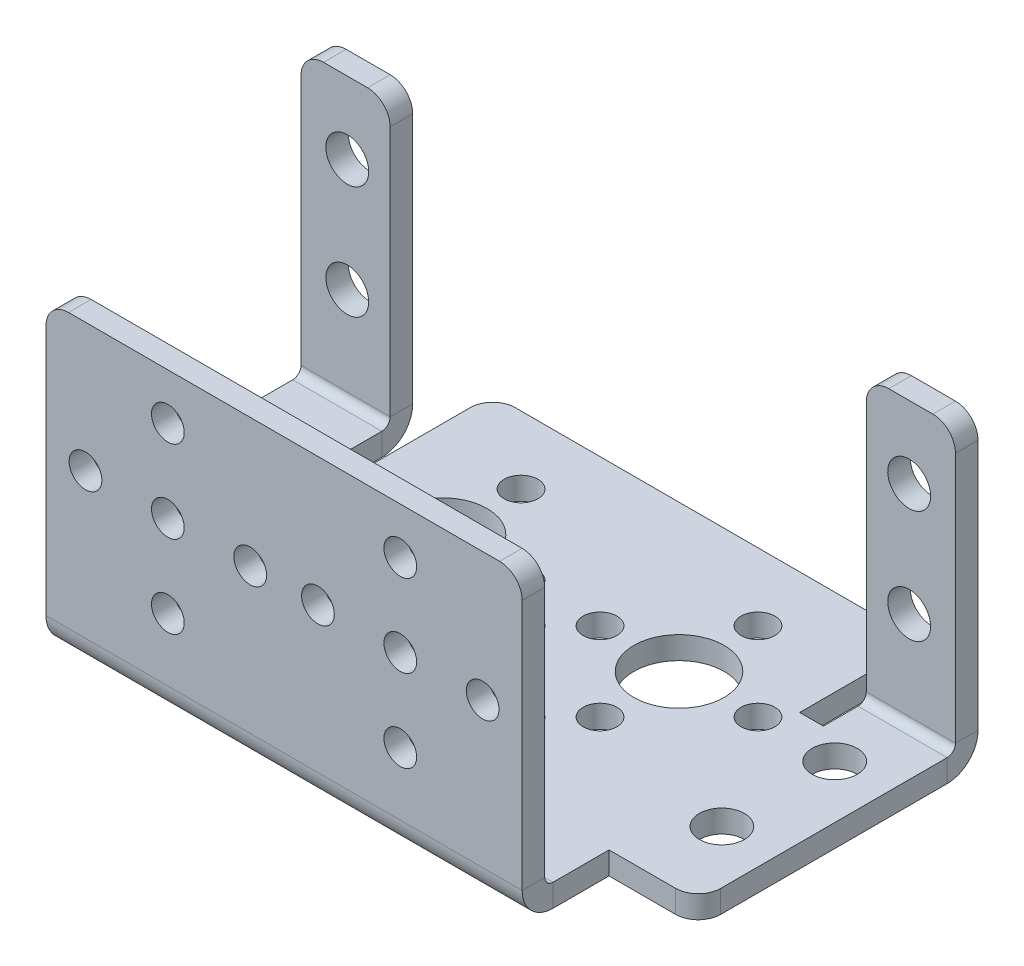
SolidWorks part; units mm, degrees
note: The reader was unsure of these and kept them because the rebuilt part matched: flange length of "边线-法兰1", "边线-法兰2".
ref_plane "前视基准面" through (0, 0, 0) normal (0, 0, 1) x (1, 0, 0)
ref_plane "上视基准面" through (0, 0, 0) normal (0, 1, 0) x (1, 0, 0)
ref_plane "右视基准面" through (0, 0, 0) normal (1, 0, 0) x (0, 0, -1)
sketch "草图2" plane through (0, 0, 0) normal (0, 1, 0) x (1, 0, 0)
  line L0 (0, 27.8382) -> (0, -27.1577) construction
  line L1 (-17, 23.49) -> (17, 23.49)
  line L2 (19, 21.49) -> (19, 12.7)
  line L3 (19, 12.7) -> (21.1, 12.7)
  line L4 (21.1, 12.7) -> (21.1, 16.5)
  line L5 (21.1, 16.5) -> (29, 16.5)
  line L6 (29, 16.5) -> (29, -4.3)
  line L7 (27, -6.3) -> (21.1, -6.3)
  line L8 (21.1, -6.3) -> (21.1, -12)
  line L9 (21.1, -12) -> (-21.1, -12)
  line L10 (-21.1, -12) -> (-21.1, -6.3)
  line L11 (-21.1, -6.3) -> (-27, -6.3)
  line L12 (-29, -4.3) -> (-29, 16.5)
  line L13 (-29, 16.5) -> (-21.1, 16.5)
  line L14 (-21.1, 16.5) -> (-21.1, 12.7)
  line L15 (-21.1, 12.7) -> (-19, 12.7)
  line L16 (-19, 12.7) -> (-19, 21.49)
  arc A22 (29, -4.3) -> (27, -6.3) centre (27, -4.3) cw
  arc A23 (-27, -6.3) -> (-29, -4.3) centre (-27, -4.3) cw
  arc A24 (17, 23.49) -> (19, 21.49) centre (17, 21.49) cw
  arc A25 (-17, 23.49) -> (-19, 21.49) centre (-17, 21.49) ccw
  point P20 (0, -12)
  point P21 (0, 23.49)
  point P45 (29, -6.3)
  point P52 (0, 0)
  dimension "D25" = 2
  dimension "D27" = 2
  dimension "D1" = 42.2
  dimension "D3" = 58
  dimension "D4" = 28.5
  dimension "D5" = 35.49
  dimension "D6" = 29
  dimension "D7" = 22.8
  dimension "D8" = 3.8
  dimension "D9" = 12
  dimension "D26" = 38
base flange "基体-法兰1" sketch "草图2" thickness 2 reverse thickness direction no parameters "D1"=0.7366
edge flange "边线-法兰1" sketch "草图9" flange angle 90 flange length 27 flange position material outside bend radius 0.7366 thickness 2 relief rectangular parameters "D6"=10
sketch "草图9" plane through (0, 0, 12) normal (0, 0, 1) x (1, 0, 0)
  line L0 (-21.1, -2) -> (21.1, -2) construction
  line L2 (-21.1, 0) -> (-21.1, 23)
  line L3 (-19.1, 25) -> (19.1, 25)
  line L4 (21.1, 23) -> (21.1, 0)
  line L7 (-21.1, 0) -> (21.1, 0) construction
  line L8 (-21.1, 0) -> (21.1, 0)
  arc A11 (19.1, 25) -> (21.1, 23) centre (19.1, 23) cw
  arc A12 (-21.1, 23) -> (-19.1, 25) centre (-19.1, 23) cw
  dimension "D7" = 2
  dimension "D8" = 27
bend "边线折弯1" bend radius 0.7366 bend angle 90 parameters "D5"=1
edge flange "边线-法兰2" sketch "草图14" flange profiles "草图14", "草图15" flange angle 90 flange length 27 flange position material outside bend radius 0.7366 thickness 2 relief rectangular parameters "D6"=10, "D8"=1
sketch "草图14" plane through (0, 0, -16.5) normal (0, 0, -1) x (-1, 0, 0)
  line L0 (21.1, 0) -> (29, 0) construction
  line L1 (21.1, 0) -> (29, 0)
  line L2 (21.1, 0) -> (21.1, 23)
  line L3 (23.1, 25) -> (27, 25)
  line L4 (29, 23) -> (29, 0)
  line L5 (21.1, -2) -> (29, -2) construction
  circle A0 centre (24.9, 18.6) radius 1.9
  circle A1 centre (24.9, 8.6) radius 1.9
  arc A2 (27, 25) -> (29, 23) centre (27, 23) cw
  arc A3 (21.1, 23) -> (23.1, 25) centre (23.1, 23) cw
  dimension "D1" = 3.8
  dimension "D3" = 6.4
  dimension "D6" = 2
  dimension "D2" = 10
  dimension "D4" = 3.8
  dimension "D5" = 27
sketch "草图15" plane through (0, 0, -16.5) normal (0, 0, -1) x (-1, 0, 0)
  line L0 (-29, 0) -> (-21.1, 0) construction
  line L1 (-29, 0) -> (-21.1, 0)
  line L2 (-29, 0) -> (-29, 23)
  line L3 (-27, 25) -> (-23.1, 25)
  line L4 (-21.1, 23) -> (-21.1, 0)
  line L5 (-29, -2) -> (-21.1, -2) construction
  circle A0 centre (-24.9, 18.6) radius 1.9
  circle A1 centre (-24.9, 8.6) radius 1.9
  arc A2 (-23.1, 25) -> (-21.1, 23) centre (-23.1, 23) cw
  arc A3 (-29, 23) -> (-27, 25) centre (-27, 23) cw
  dimension "D1" = 3.8
  dimension "D6" = 2
  dimension "D2" = 3.8
  dimension "D3" = 10
  dimension "D4" = 27
  dimension "D5" = 6.4
bend "边线折弯2" bend radius 0.7366 bend angle 90 parameters "D5"=2
bend "边线折弯3" bend radius 0.7366 bend angle 90 parameters "D5"=3
hole_wizard "Ø8.0 (8) 直径孔1" positions "草图16" profile "草图17" hole size "Ø8.0" standard "GB" end condition through all
sketch "草图16" plane through (0, 0, 0) normal (0, 1, 0) x (1, 0, 0)
  line L0 (-10.5, 10.5) -> (0, 0) construction
  line L1 (0, 0) -> (10.5, 10.5) construction
  point P0 (0, 0)
  point P3 (-10.5, 10.5)
  point P5 (10.5, 10.5)
  dimension "D1" = 21
  dimension "D2" = 10.5
  dimension "D3" = 90
sketch "草图17" plane through (0, 0, 0) normal (1, 0, 0) x (0, 0, 1)
  line L0 (0, 0) -> (0, 2)
  line L1 (0, 2) -> (4, 2)
  line L2 (4, 2) -> (4, 0)
  line L5 (4, 0) -> (0, 0)
  line L11 (0, -6.35) -> (0, 107.95) construction
  dimension "通孔孔直径" = 8
  dimension "通孔孔深度" = 2
hole_wizard "Ø3.0 (3) 直径孔1" positions "草图20" profile "草图19" hole size "Ø3.0" standard "GB" end condition through all
sketch "草图20" plane through (0, 0, 0) normal (0, 1, 0) x (1, 0, 0)
  circle A0 centre (-10.5, 10.5) radius 7 construction
  circle A1 centre (10.5, 10.5) radius 7 construction
  circle A2 centre (0, 0) radius 7 construction
  point P0 (0, -7)
  point P2 (-17.5, 10.5)
  point P4 (17.5, 10.5)
  point P22 (-3.5, 10.5)
  point P24 (-10.5, 17.5)
  point P26 (-10.5, 3.5)
  point P28 (0, 7)
  point P30 (-7, 0)
  point P32 (7, 0)
  point P34 (10.5, 3.5)
  point P36 (3.5, 10.5)
  point P38 (10.5, 17.5)
  dimension "D1" = 14
sketch "草图19" plane through (0, 0, 7) normal (1, 0, 0) x (0, 0, 1)
  line L0 (0, 0) -> (0, 2)
  line L1 (0, 2) -> (1.5, 2)
  line L2 (1.5, 2) -> (1.5, 0)
  line L5 (1.5, 0) -> (0, 0)
  line L11 (0, -6.35) -> (0, 107.95) construction
  dimension "通孔孔直径" = 3
  dimension "通孔孔深度" = 2
hole_wizard "Ø4.0 (4) 直径孔1" positions "草图21" profile "草图22" hole size "Ø4.0" standard "GB" end condition through all
sketch "草图21" plane through (0, 0, 0) normal (0, 1, 0) x (1, 0, 0)
  line L3 (19.1, -12) -> (-19.1, -12) construction
  point P0 (-24.3, 10.5)
  point P2 (-24.3, 0.5)
  point P4 (24.3, 10.5)
  point P6 (24.3, 0.5)
  dimension "D1" = 10
  dimension "D2" = 12.5
  dimension "D3" = 48.6
  dimension "D4" = 24.3
sketch "草图22" plane through (-24.3, 0, -10.5) normal (1, 0, 0) x (0, 0, 1)
  line L0 (0, 0) -> (0, 2)
  line L1 (0, 2) -> (2, 2)
  line L2 (2, 2) -> (2, 0)
  line L5 (2, 0) -> (0, 0)
  line L11 (0, -6.35) -> (0, 107.95) construction
  dimension "通孔孔直径" = 4
  dimension "通孔孔深度" = 2
sketch "草图24" plane through (0, 0, -18.5) normal (0, 0, -1) x (-1, 0, 0)
  line L0 (-24.9, 18.6) -> (-24.9, 8.6) construction
ref_point "点4"
ref_plane "基准面2" through (0, 13.6, 0) normal (0, 1, 0) x (1, 0, 0)
hole_wizard "Ø2.9 (2.9) 直径孔2" positions "草图30" profile "草图29" hole size "Ø2.9" standard "GB" end condition through all
sketch "草图30" plane through (0, 0, 14) normal (0, 0, 1) x (1, 0, 0)
  line L7 (-21.1, 23) -> (-21.1, 0.7366) construction
  circle A1 centre (10.3, 13.6) radius 7.3 construction
  circle A2 centre (-10.3, 13.6) radius 7.3 construction
  point P0 (10.3, 13.6)
  point P13 (-10.3, 13.6)
  point P16 (-10.3, 20.9)
  point P18 (-17.6, 13.6)
  point P20 (-10.3, 6.3)
  point P22 (-3, 13.6)
  point P24 (3, 13.6)
  point P26 (10.3, 20.9)
  point P30 (10.3, 6.3)
  point P77 (17.6, 13.6)
  dimension "D1" = 14.6
  dimension "D2" = 14.6
  dimension "D3" = 3.5
sketch "草图29" plane through (10.3, 13.6, 14) normal (1, 0, 0) x (0, -1, 0)
  line L0 (0, 0) -> (0, 37.49)
  line L1 (0, 37.49) -> (1.45, 37.49)
  line L2 (1.45, 37.49) -> (1.45, 0)
  line L5 (1.45, 0) -> (0, 0)
  line L11 (0, -6.35) -> (0, 107.95) construction
  dimension "通孔孔直径" = 2.9
  dimension "通孔孔深度" = 37.49
sketch "折弯-线1" [suppressed] plane through (0, 0, 0) normal (0, 1, 0) x (1, 0, 0)
sketch "边界框1" [suppressed] plane through (0, 0, 0) normal (0, 1, 0) x (1, 0, 0)
sheet metal parameters "钣金1" thickness 2 parameters "D1"=0.7366
flat pattern "平板型式1" [suppressed]
sketch "折弯-线2" plane through (0, 0, 0) normal (0, 1, 0) x (1, 0, 0)
sketch3d "边界框2" [suppressed]
  line L0 (-2, 27.79, 0) -> (56, 27.79, 0) construction
  line L1 (-2, -7.7, 0) -> (56, -7.7, 0) construction
  line L2 (-2, 27.79, 0) -> (-2, -7.7, 0) construction
  line L3 (56, 27.79, 0) -> (56, -7.7, 0) construction
sheet metal parameters "钣金2" thickness 2 parameters "D1"=0.7366
flat pattern "平板型式1"
sketch "折弯-线2" plane through (0, 0, 0) normal (0, 1, 0) x (1, 0, 0)
  line L0 (-21.1, -12.6273) -> (21.1, -12.6273) construction
  line L1 (-21.1, -12.6273) -> (21.1, -12.6273) construction
sketch3d "边界框2" [suppressed]
  line L0 (2, -34.017, 0) -> (2, 27.79, 0) construction
  line L1 (-56, -34.0171, 0) -> (-56, 27.79, 0) construction
  line L2 (2, -34.017, 0) -> (-56, -34.0171, 0) construction
  line L3 (2, 27.79, 0) -> (-56, 27.79, 0) construction
bend of the flat pattern "展开-<边线折弯1>1"
sheet metal parameters "钣金3" thickness 2 parameters "D1"=0.7366
flat pattern "平板型式1"
sketch "折弯-线2" plane through (0, 0, 0) normal (0, 1, 0) x (1, 0, 0)
  line L0 (-21.1, -12.6273) -> (21.1, -12.6273) construction
  line L1 (-21.1, -12.6273) -> (21.1, -12.6273) construction
  line L2 (29, 17.1273) -> (21.1, 17.1273) construction
  line L3 (-21.1, 17.1273) -> (-29, 17.1273) construction
  line L4 (29, 17.1273) -> (21.1, 17.1273) construction
  line L5 (-21.1, 17.1273) -> (-29, 17.1273) construction
sketch3d "边界框2" [suppressed]
  line L0 (2, -34.017, 0) -> (2, 47.0546, 0) construction
  line L1 (-56, -34.0171, 0) -> (-56, 47.0546, 0) construction
  line L2 (2, -34.017, 0) -> (-56, -34.0171, 0) construction
  line L3 (2, 47.0546, 0) -> (-56, 47.0546, 0) construction
bend of the flat pattern "展开-<边线折弯1>1"
bend of the flat pattern "展开-<边线折弯2>1"
bend of the flat pattern "展开-<边线折弯3>1"
sheet metal parameters "钣金4" thickness 2 parameters "D1"=0.7366
flat pattern "平板型式1"
sketch "折弯-线2" plane through (0, 0, 0) normal (0, 1, 0) x (1, 0, 0)
  line L0 (-21.1, -12.6273) -> (21.1, -12.6273) construction
  line L1 (-21.1, -12.6273) -> (21.1, -12.6273) construction
  line L2 (29, 17.1273) -> (21.1, 17.1273) construction
  line L3 (-21.1, 17.1273) -> (-29, 17.1273) construction
  line L4 (29, 17.1273) -> (21.1, 17.1273) construction
  line L5 (-21.1, 17.1273) -> (-29, 17.1273) construction
sketch3d "边界框2" [suppressed]
  line L0 (2, -34.017, 0) -> (2, 47.0546, 0) construction
  line L1 (-56, -34.0171, 0) -> (-56, 47.0546, 0) construction
  line L2 (2, -34.017, 0) -> (-56, -34.0171, 0) construction
  line L3 (2, 47.0546, 0) -> (-56, 47.0546, 0) construction
bend of the flat pattern "展开-<边线折弯1>1"
bend of the flat pattern "展开-<边线折弯2>1"
bend of the flat pattern "展开-<边线折弯3>1"
sheet metal parameters "钣金5" thickness 2 parameters "D1"=0.7366
flat pattern "平板型式1"
sketch "折弯-线2" plane through (0, 0, 0) normal (0, 1, 0) x (1, 0, 0)
  line L0 (-21.1, -12.6273) -> (21.1, -12.6273) construction
  line L1 (-21.1, -12.6273) -> (21.1, -12.6273) construction
  line L2 (29, 17.1273) -> (21.1, 17.1273) construction
  line L3 (-21.1, 17.1273) -> (-29, 17.1273) construction
  line L4 (29, 17.1273) -> (21.1, 17.1273) construction
  line L5 (-21.1, 17.1273) -> (-29, 17.1273) construction
sketch3d "边界框2" [suppressed]
  line L0 (2, -34.017, 0) -> (2, 47.0546, 0) construction
  line L1 (-56, -34.0171, 0) -> (-56, 47.0546, 0) construction
  line L2 (2, -34.017, 0) -> (-56, -34.0171, 0) construction
  line L3 (2, 47.0546, 0) -> (-56, 47.0546, 0) construction
bend of the flat pattern "展开-<边线折弯1>1"
bend of the flat pattern "展开-<边线折弯2>1"
bend of the flat pattern "展开-<边线折弯3>1"
sheet metal parameters "钣金7" thickness 2 parameters "D1"=0.7366
flat pattern "平板型式1" [suppressed]
sketch "折弯-线2" plane through (0, 0, 0) normal (0, 1, 0) x (1, 0, 0)
  line L0 (-21.1, -12.6273) -> (21.1, -12.6273) construction
  line L1 (-21.1, -12.6273) -> (21.1, -12.6273) construction
  line L2 (29, 17.1273) -> (21.1, 17.1273) construction
  line L3 (-21.1, 17.1273) -> (-29, 17.1273) construction
  line L4 (29, 17.1273) -> (21.1, 17.1273) construction
  line L5 (-21.1, 17.1273) -> (-29, 17.1273) construction
sketch3d "边界框2" [suppressed]
  line L0 (2, -33.9546, 0) -> (2, 47.0546, 0) construction
  line L1 (-56, -33.9547, 0) -> (-56, 47.0546, 0) construction
  line L2 (2, -33.9546, 0) -> (-56, -33.9547, 0) construction
  line L3 (2, 47.0546, 0) -> (-56, 47.0546, 0) construction
bend of the flat pattern "展开-<边线折弯1>1"
bend of the flat pattern "展开-<边线折弯2>1"
bend of the flat pattern "展开-<边线折弯3>1"
sketch "草图24-1" plane through (0, -2, -17.7546) normal (0, -1, 0) x (-1, 0, 0)
  line L0 (-24.9, 18.6) -> (-24.9, 8.6) construction
sheet metal parameters "钣金9" thickness 2 parameters "D1"=0.7366
flat pattern "平板型式1" [suppressed]
sketch "折弯-线2" plane through (0, 0, 0) normal (0, 1, 0) x (1, 0, 0)
  line L0 (-21.1, -12.6273) -> (21.1, -12.6273) construction
  line L1 (-21.1, -12.6273) -> (21.1, -12.6273) construction
  line L2 (29, 17.1273) -> (21.1, 17.1273) construction
  line L3 (-21.1, 17.1273) -> (-29, 17.1273) construction
  line L4 (29, 17.1273) -> (21.1, 17.1273) construction
  line L5 (-21.1, 17.1273) -> (-29, 17.1273) construction
sketch3d "边界框2" [suppressed]
  line L0 (2, -33.9546, 0) -> (2, 47.0546, 0) construction
  line L1 (-56, -33.9547, 0) -> (-56, 47.0546, 0) construction
  line L2 (2, -33.9546, 0) -> (-56, -33.9547, 0) construction
  line L3 (2, 47.0546, 0) -> (-56, 47.0546, 0) construction
bend of the flat pattern "展开-<边线折弯1>1"
bend of the flat pattern "展开-<边线折弯2>1"
bend of the flat pattern "展开-<边线折弯3>1"
sketch "草图24-1" plane through (0, -2, -17.7546) normal (0, -1, 0) x (-1, 0, 0)
  line L0 (-24.9, 18.6) -> (-24.9, 8.6) construction
